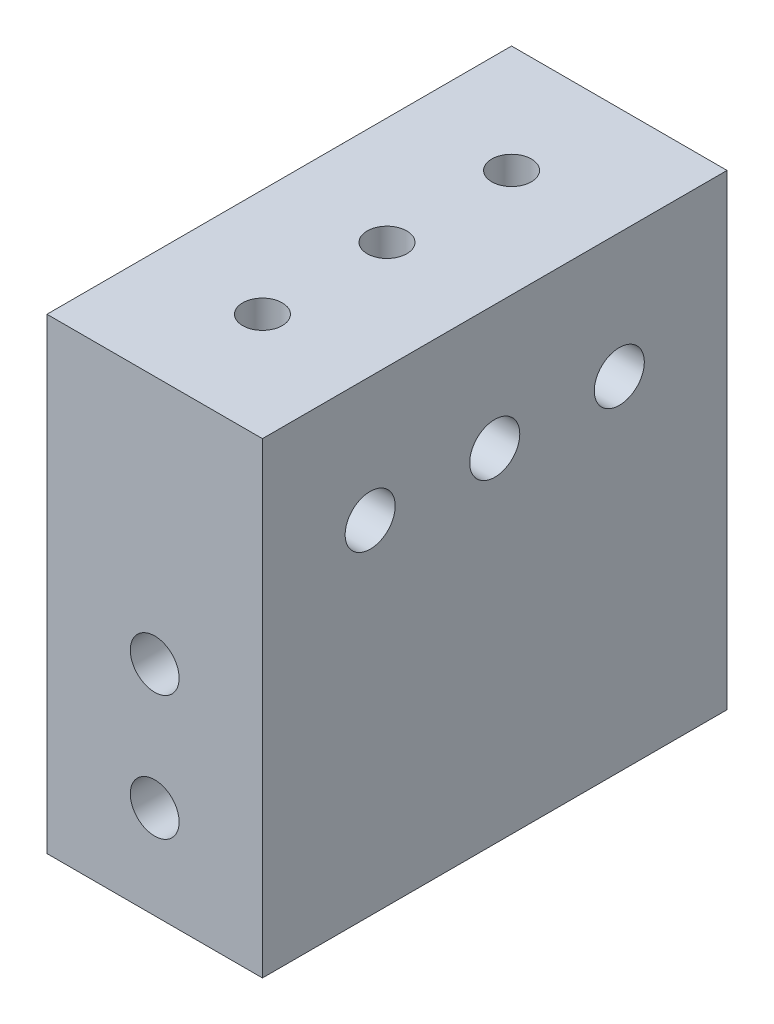
SolidWorks part; units mm, degrees
other "Markup1"
sketch "Sketch3" plane through (12.6365, 38.1, -23.749) normal (0.9027, 0.4189, -0.0984) x (-0.0151, -0.1977, -0.9801)
sketch "Sketch7" plane through (11.049, 23.8125, -23.749) normal (0.9027, 0.4189, -0.0984) x (-0.0151, -0.1977, -0.9801)
sketch "Sketch9" plane through (11.049, 23.8125, -23.749) normal (0.9027, 0.4189, -0.0984) x (-0.0151, -0.1977, -0.9801)
sketch "Sketch12" plane through (11.049, 23.8125, -23.749) normal (0.9027, 0.4189, -0.0984) x (-0.0151, -0.1977, -0.9801)
sketch "Sketch15" plane through (11.049, 23.8125, -23.749) normal (0.9027, 0.4189, -0.0984) x (-0.0151, -0.1977, -0.9801)
other "Markup2"
sketch "Sketch4" plane through (12.6365, 38.1, -23.749) normal (0.9027, 0.4189, -0.0984) x (-0.0151, -0.1977, -0.9801)
sketch "Sketch8" plane through (11.049, 23.8125, -23.749) normal (0.9027, 0.4189, -0.0984) x (-0.0151, -0.1977, -0.9801)
sketch "Sketch10" plane through (11.049, 23.8125, -23.749) normal (0.9027, 0.4189, -0.0984) x (-0.0151, -0.1977, -0.9801)
sketch "Sketch13" plane through (11.049, 23.8125, -23.749) normal (0.9027, 0.4189, -0.0984) x (-0.0151, -0.1977, -0.9801)
sketch "Sketch16" plane through (11.049, 23.8125, -23.749) normal (0.9027, 0.4189, -0.0984) x (-0.0151, -0.1977, -0.9801)
other "Markup3"
sketch "Sketch11" plane through (11.049, 23.8125, -23.749) normal (1, 0.0033, -0.0037) x (-0.003, -0.1893, -0.9819)
sketch "Sketch14" plane through (11.049, 23.8125, -23.749) normal (1, 0.0033, -0.0037) x (-0.003, -0.1893, -0.9819)
sketch "Sketch17" plane through (11.049, 23.8125, -23.749) normal (1, 0.0033, -0.0037) x (-0.003, -0.1893, -0.9819)
material "6061-T6 (SS)"
ref_plane "Front Plane" through (0, 0, 0) normal (0, 0, 1) x (1, 0, 0)
ref_plane "Top Plane" through (0, 0, 0) normal (0, 1, 0) x (1, 0, 0)
ref_plane "Right Plane" through (0, 0, 0) normal (1, 0, 0) x (0, 0, -1)
sketch "Sketch1" plane through (0, 0, 0) normal (0, 1, 0) x (1, 0, 0)
  line L0 (-12.573, 25.273) -> (12.573, 25.273)
  line L1 (-10.9855, -23.6855) -> (10.9855, -23.6855)
  line L2 (-10.9855, -23.6855) -> (-10.9855, 23.6855)
  line L3 (-10.9855, 23.6855) -> (10.9855, 23.6855)
  line L4 (10.9855, -23.6855) -> (10.9855, 23.6855)
  line L5 (-10.9855, -23.6855) -> (10.9855, 23.6855) construction
  line L6 (-10.9855, 23.6855) -> (10.9855, -23.6855) construction
  line L7 (12.573, -25.273) -> (12.573, 25.273)
  line L8 (-12.573, -25.273) -> (12.573, -25.273)
  line L9 (-12.573, -25.273) -> (-12.573, 25.273)
  point P0 (0, 0)
  dimension "D1" = 21.971
  dimension "D2" = 47.371
  dimension "D3" = 1.5875
extrude "Boss-Extrude1" add sketch "Sketch1" along normal mid plane 47.625 contours L1 L4 L3 L2 region at (0, 0, 0)
sketch "Sketch2" plane through (10.9855, 0, 0) normal (1, 0, 0) x (0, 0, -1)
  line L0 (-23.6855, 23.8125) -> (23.6855, 23.8125) construction
  line L4 (-25.4, -23.8125) -> (25.4, -23.8125) construction
  line L5 (-25.4, -23.8125) -> (-25.4, 23.8125) construction
  line L6 (-25.4, 23.8125) -> (25.4, 23.8125) construction
  line L7 (25.4, -23.8125) -> (25.4, 23.8125) construction
  line L8 (-25.4, -23.8125) -> (25.4, 23.8125) construction
  line L9 (-25.4, 23.8125) -> (25.4, -23.8125) construction
  circle A0 centre (-12.7, 11.1125) radius 2.5527
  circle A1 centre (0, 11.1125) radius 2.5527
  circle A2 centre (12.7, 11.1125) radius 2.5527
  point P6 (0, 0)
  dimension "D1" = 5.1054
  dimension "D2" = 50.8
  dimension "D4" = 25.4
  dimension "D5" = 12.7
  dimension "D6" = 38.1
  dimension "D7" = 12.7
  dimension "D8" = 12.7
  dimension "D9" = 12.7
extrude "Cut-Extrude1" cut sketch "Sketch2" against normal through all
sketch "Sketch5" plane through (0, 0, -23.6855) normal (0, 0, -1) x (-1, 0, 0)
  line L0 (10.9855, 23.8125) -> (-10.9855, 23.8125) construction
  line L1 (-12.7, -23.8125) -> (12.7, -23.8125) construction
  line L2 (-12.7, -23.8125) -> (-12.7, 23.8125) construction
  line L3 (-12.7, 23.8125) -> (12.7, 23.8125) construction
  line L4 (12.7, -23.8125) -> (12.7, 23.8125) construction
  line L5 (-12.7, -23.8125) -> (12.7, 23.8125) construction
  line L6 (-12.7, 23.8125) -> (12.7, -23.8125) construction
  circle A0 centre (0, -1.5875) radius 2.4892
  circle A2 centre (0, -14.2875) radius 2.4892
  point P0 (0, 0)
  dimension "D5" = 38.1
  dimension "D7" = 4.9784
  dimension "D8" = 4.9784
  dimension "D1" = 25.4
  dimension "D3" = 25.4
  dimension "D4" = 12.7
  dimension "D6" = 12.7
extrude "Cut-Extrude2" cut sketch "Sketch5" against normal through all
hole_wizard "#10-32 Tapped Hole1" positions "3DSketch1" profile "Sketch18" tap size "#10-32" standard "ANSI Inch" end condition through all
sketch3d "3DSketch1"
  line L0 (0, 23.8125, 23.6855) -> (0, 23.8125, -23.6855) construction
  line L1 (-10.9855, 23.8125, 23.6855) -> (10.9855, 23.8125, 23.6855) construction
  line L2 (-10.9855, 23.8125, -23.6855) -> (10.9855, 23.8125, -23.6855) construction
  point P0 (0, 23.8125, 12.7)
  point P5 (0, 23.8125, -12.7)
  point P9 (0, 23.8125, 0)
  point P21 (-2.401, 23.8125, -14.553)
  point P22 (0, 0, 0)
  point P26 (2.0713, 23.8125, 0.1593)
  point P28 (0, 0, 0)
  dimension "D1" = 12.7
  dimension "D2" = 12.7
cosmetic thread "Hole Thread1" parameters "D1"=9.652, "D2"=4.826
cosmetic thread "Hole Thread2" parameters "D1"=9.652, "D2"=4.826
cosmetic thread "Hole Thread3" parameters "D1"=9.652, "D2"=4.826
sketch "Sketch18" plane through (0, 23.8125, 12.7) normal (1, 0, 0) x (0, 0, 1)
  line L0 (0, 0) -> (0, 47.625)
  line L1 (0, 47.625) -> (2.0193, 47.625)
  line L2 (2.0193, 47.625) -> (2.0193, 0)
  line L5 (2.0193, 0) -> (0, 0)
  line L11 (0, -6.35) -> (0, 107.95) construction
  dimension "Thru Tap Drill Dia." = 4.0386
  dimension "Thru Tap Drill Depth" = 47.625
